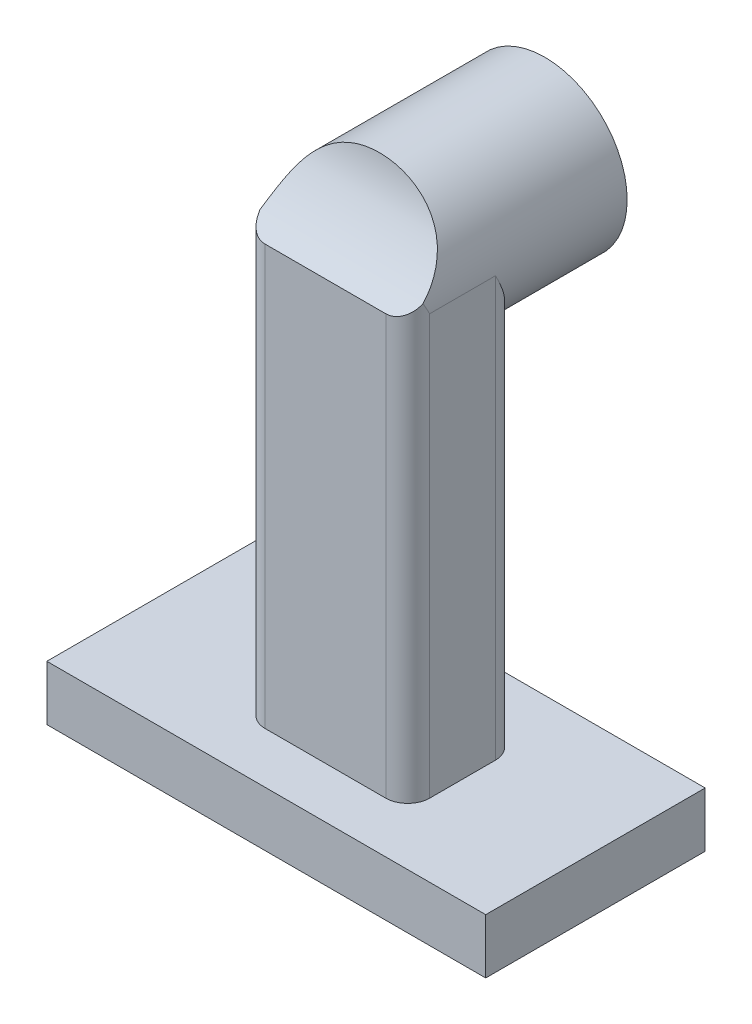
SolidWorks part; units mm, degrees
ref_plane "Ön Düzlem" through (0, 0, 0) normal (0, 0, 1) x (1, 0, 0)
ref_plane "Üst Düzlem" through (0, 0, 0) normal (0, 1, 0) x (1, 0, 0)
ref_plane "Sağ Düzlem" through (0, 0, 0) normal (1, 0, 0) x (0, 0, -1)
sketch "Çizim1" plane through (0, 0, 0) normal (0, 0, 1) x (1, 0, 0)
  circle A0 centre (0, 31.7143) radius 7.5
  dimension "D1" = 15
extrude "Yükseklik-Ekstrüzyon1" add sketch "Çizim1" along normal blind 15
sketch "Çizim2" plane through (0, 0, 15) normal (0, 0, 1) x (1, 0, 0)
  line L0 (-7.5, 31.7143) -> (7.5, 31.7143)
  line L1 (7.5, 31.7143) -> (7.5, -6.5224)
  line L2 (7.5, -6.5224) -> (-7.5, -6.5224)
  line L3 (-7.5, -6.5224) -> (-7.5, 31.7143)
  circle A0 centre (0, 31.7143) radius 7.5 construction
extrude "Yükseklik-Ekstrüzyon2" add sketch "Çizim2" along normal blind 5 and the other way blind 5
fillet "Radyus1" radius 10 1 edges at (0, 31.7143, 15)
fillet "Radyus2" radius 2 4 edges at (-7.5, 12.596, 10) (-7.5, 12.596, 20) (7.5, 12.596, 20) (7.5, 12.596, 10)
sketch "Çizim3" plane through (0, 0, 0) normal (0, 0, -1) x (-1, 0, 0)
  circle A0 centre (0, 31.7143) radius 3.5
  dimension "D1" = 7
extrude "Kes-Ekstrüzyon1" cut sketch "Çizim3" against normal blind 10
sketch "Çizim4" plane through (0, -6.5224, 0) normal (0, -1, 0) x (-1, 0, 0)
  line L1 (20.752, -4.6385) -> (-19.248, -4.6385)
  line L2 (20.752, -4.6385) -> (20.752, -24.6385)
  line L3 (20.752, -24.6385) -> (-19.248, -24.6385)
  line L4 (-19.248, -4.6385) -> (-19.248, -24.6385)
  line L5 (20.752, -4.6385) -> (-19.248, -24.6385) construction
  line L6 (20.752, -24.6385) -> (-19.248, -4.6385) construction
  point P0 (0.752, -14.6385)
  dimension "D1" = 40
  dimension "D2" = 20
extrude "Yükseklik-Ekstrüzyon3" add sketch "Çizim4" along normal blind 5
